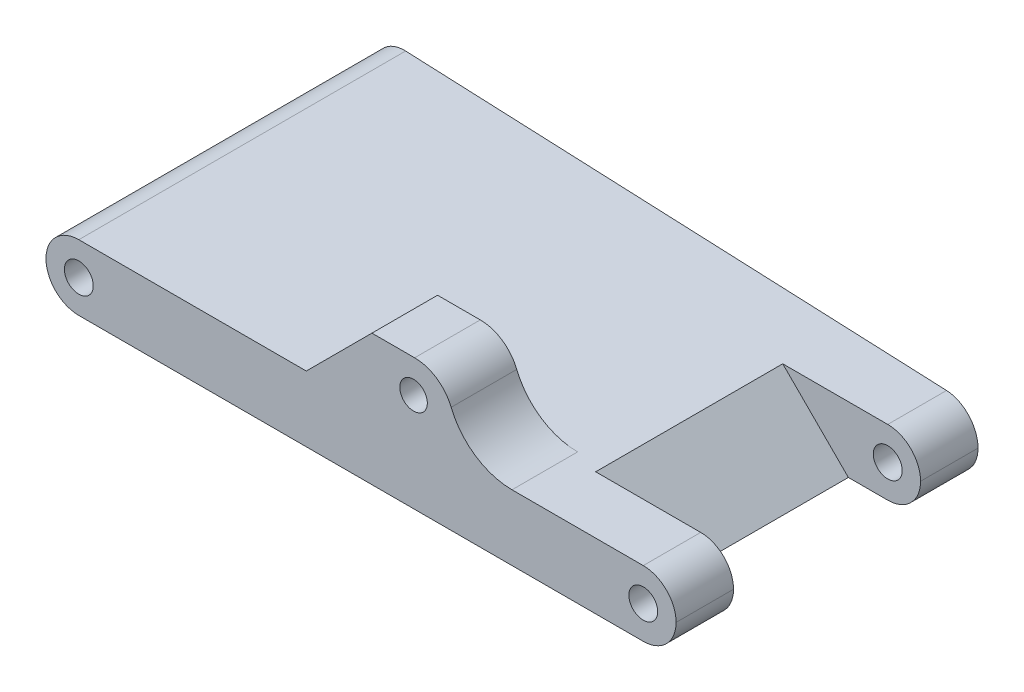
SolidWorks part; units mm, degrees
ref_plane "Front Plane" through (0, 0, 0) normal (0, 0, 1) x (1, 0, 0)
ref_plane "Top Plane" through (0, 0, 0) normal (0, 1, 0) x (1, 0, 0)
ref_plane "Right Plane" through (0, 0, 0) normal (1, 0, 0) x (0, 0, -1)
sketch "Sketch1" plane through (0, 0, 0) normal (0, 1, 0) x (1, 0, 0)
  line L0 (-27.614, 0) -> (20.386, 0)
  line L1 (-27.614, 0) -> (-27.614, 25)
  line L2 (20.386, 0) -> (20.386, 23)
  line L3 (-27.614, 25) -> (20.386, 23)
  dimension "D1" = 48
  dimension "D2" = 25
  dimension "D3" = 23
extrude "Boss-Extrude1" add sketch "Sketch1" along normal blind 5
sketch "Sketch3" plane through (0, 0, 0) normal (0, 0, 1) x (1, 0, 0)
  line L0 (-27.614, 2.5) -> (-25.114, 2.5) construction
  line L1 (-27.614, 5) -> (-27.614, 0) construction
  line L2 (20.386, 5) -> (20.386, 0) construction
  line L3 (17.886, 2.5) -> (20.386, 2.5) construction
  circle A0 centre (-25.114, 2.5) radius 1.1
  circle A1 centre (17.886, 2.5) radius 1.1
  dimension "D1" = 2.5
  dimension "D2" = 2.5
extrude "Cut-Extrude1" cut sketch "Sketch3" against normal up to surface (24.85 mm away) up to face at (-3.614, 2.5, -24)
fillet "Fillet1" radius 2.5 4 edges at (20.386, 0, -11.5) (20.386, 5, -11.5) (-27.614, 0, -12.5) (-27.614, 5, -12.5)
sketch "Sketch4" plane through (0, 0, 0) normal (0, 0, 1) x (1, 0, 0)
  line L0 (-25.114, 5) -> (17.886, 5) construction
  line L1 (-25.114, 5) -> (17.886, 5) construction
  line L2 (-7.785, 5) -> (-2.785, 10)
  line L3 (-2.785, 10) -> (2.886, 10)
  line L4 (-4.2495, 1.4645) -> (-0.714, 5)
  line L5 (-0.714, 5) -> (2.886, 5)
  line L6 (2.886, 10) -> (2.886, 5)
  line L7 (-7.785, 5) -> (-4.2495, 1.4645)
  line L8 (2.886, 7.5) -> (0.386, 7.5) construction
  line L9 (-0.714, 5) -> (-0.714, 7.5) construction
  circle A0 centre (0.386, 7.5) radius 1.1
  dimension "D3" = 2.2
  dimension "D4" = 2.5
  dimension "D1" = 5
  dimension "D2" = 45
  dimension "D5" = 20
ref_plane "Plane1" through (0, 0, -23) normal (0, 0, 1) x (1, 0, 0)
ref_plane "Plane2" through (0, 0, -11.5) normal (0, 0, 1) x (1, 0, 0)
ref_plane "Plane3" through (0, 0, -14) normal (0, 0, 1) x (1, 0, 0)
extrude "Boss-Extrude2" add sketch "Sketch4" against normal blind 5 contours L2 L3 L6 L5 L4 L7
sketch "Sketch7" plane through (0, 0, 0) normal (0, 0, 1) x (1, 0, 0)
  line L0 (0.386, 7.4924) -> (2.886, 7.5) construction
  line L1 (2.886, 10) -> (2.886, 5) construction
  circle A0 centre (0.386, 7.4924) radius 1.05
  dimension "D1" = 2.1
  dimension "D2" = 2.5
extrude "Cut-Extrude3" cut sketch "Sketch7" against normal up to surface (5 mm away) up to face at (-1.1995, 7.5, -5)
fillet "Fillet2" radius 5 1 edges at (2.886, 5, -2.5)
sketch "Sketch8" plane through (0, 5, 0) normal (0, 1, 0) x (1, 0, 0)
  line L0 (20.386, 23) -> (17.886, 23.1042) construction
  line L1 (17.886, 0) -> (20.386, 0) construction
  line L2 (20.386, 23) -> (20.386, 0) construction
  line L3 (20.386, 23) -> (17.886, 23.1042) construction
  line L4 (17.886, 0) -> (20.386, 0) construction
  line L5 (20.386, 23) -> (20.386, 0) construction
  line L7 (20.386, 4.375) -> (14.886, 4.375)
  line L8 (20.386, 4.375) -> (20.386, 18.625)
  line L9 (20.386, 18.625) -> (14.886, 18.625)
  line L10 (14.886, 4.375) -> (14.886, 18.625)
  point P8 (20.386, 11.5)
  point P9 (20.386, 11.5)
  dimension "D1" = 14.25
  dimension "D2" = 5.5
extrude "Cut-Extrude4" cut sketch "Sketch8" against normal up to surface (5 mm away) contours L10 L9 L8 L7 up to face at (-3.614, 0, -12)
chamfer "Chamfer1" distance 5 angle 45 1 edges at (14.886, 5, -11.5)
fillet "Fillet3" radius 3 1 edges at (2.886, 10, -2.5)
